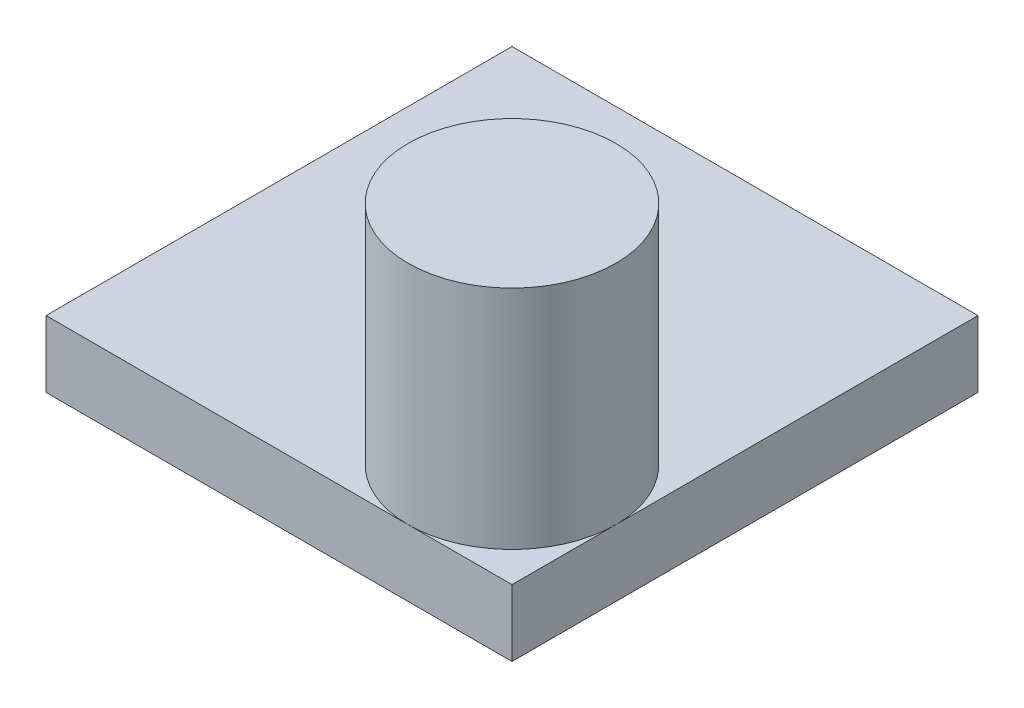
SolidWorks part; units mm, degrees
ref_plane "Front Plane" through (0, 0, 0) normal (0, 0, 1) x (1, 0, 0)
ref_plane "Top Plane" through (0, 0, 0) normal (0, 1, 0) x (1, 0, 0)
ref_plane "Right Plane" through (0, 0, 0) normal (1, 0, 0) x (0, 0, -1)
sketch "Sketch1" plane through (0, 0, 0) normal (0, 1, 0) x (1, 0, 0)
  circle A0 centre (0, 0) radius 15.6002
  dimension "D1" = 31.2004
extrude "Boss-Extrude1" add sketch "Sketch1" along normal blind 34
sketch "Sketch2" plane through (0, 0, 0) normal (0, -1, 0) x (1, 0, 0)
  line L4 (15.6002, -54.3998) -> (15.6002, 15.6002)
  line L5 (-54.3998, -54.3998) -> (15.6002, -54.3998)
  line L6 (-54.3998, 15.6002) -> (-54.3998, -54.3998)
  line L7 (15.6002, 15.6002) -> (-54.3998, 15.6002)
  line L8 (15.6002, -54.3998) -> (15.6002, 15.6002)
  line L9 (-54.3998, -54.3998) -> (15.6002, -54.3998)
  line L10 (-54.3998, 15.6002) -> (-54.3998, -54.3998)
  line L11 (15.6002, 15.6002) -> (-54.3998, 15.6002)
  dimension "D1" = 0
extrude "Boss-Extrude2" add sketch "Sketch2" along normal blind 10
equation "\"test var\"= 12 + 3"
equation "\"other var\"= 13in"
